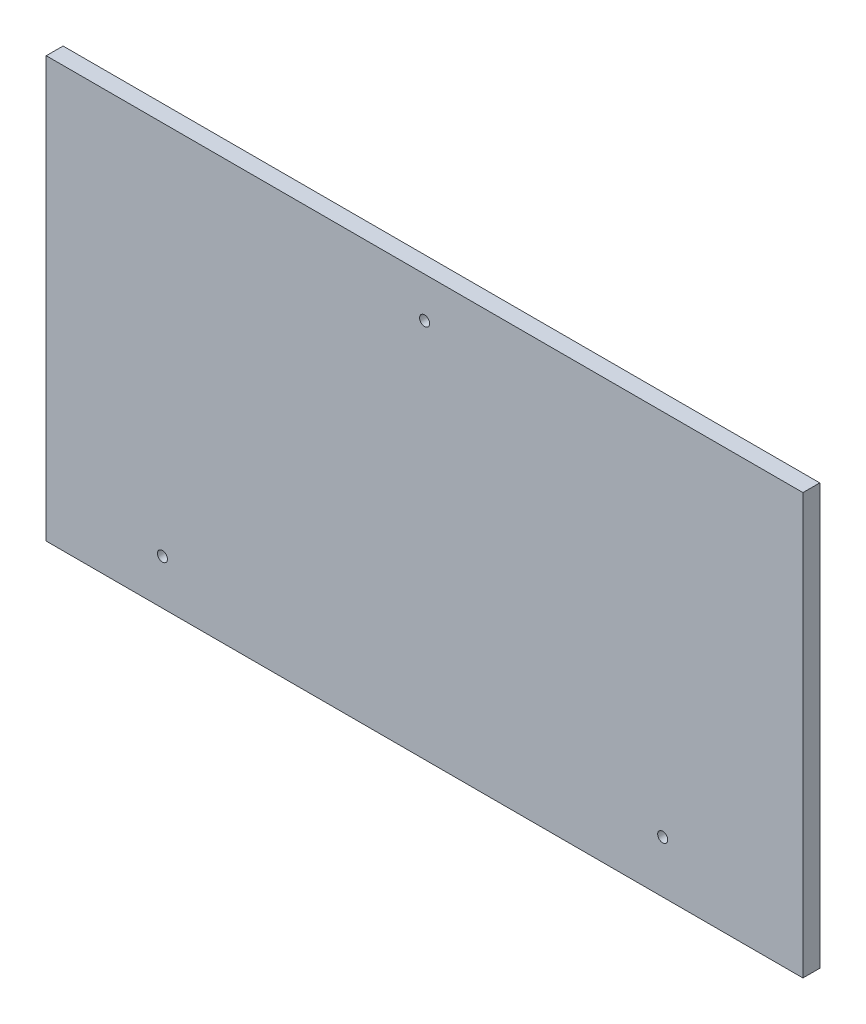
SolidWorks part; units mm, degrees
ref_plane "Ebene vorne" through (0, 0, 0) normal (0, 0, 1) x (1, 0, 0)
ref_plane "Ebene oben" through (0, 0, 0) normal (0, 1, 0) x (1, 0, 0)
ref_plane "Ebene rechts" through (0, 0, 0) normal (1, 0, 0) x (0, 0, -1)
sketch "Skizze1" plane through (0, 0, 0) normal (0, 0, 1) x (1, 0, 0)
  line L2 (225, -125) -> (-225, -125)
  line L3 (225, -125) -> (225, 125)
  line L4 (225, 125) -> (-225, 125)
  line L5 (-225, -125) -> (-225, 125)
  line L6 (225, -125) -> (-225, 125) construction
  line L7 (225, 125) -> (-225, -125) construction
  point P2 (0, 0)
  point P13 (-150.1124, -96.3474)
  point P14 (154.9547, -96.3474)
  point P15 (0, 111.7356)
  point P16 (154.9547, -96.3474)
  dimension "D1" = 450
  dimension "D2" = 250
extrude "Aufsatz-Linear austragen1" add sketch "Skizze1" along normal blind 10 contours L4 L5 L2 L3
sketch "Skizze2" plane through (0, 0, 0) normal (0, 0, -1) x (-1, 0, 0)
  point P0 (-141.608, -94.0978)
  point P1 (155.9071, -98.2492)
  point P2 (0, 101.0168)
hole_wizard "Ø6.0 (6) Durchmesser Bohrung1" positions "3D-Skizze1" profile "Skizze3" hole size "Ø6.0" standard "ISO" end condition through all
sketch3d "3D-Skizze1"
  point P0 (-155.9071, -98.2492, 0)
  point P3 (141.608, -94.0978, 0)
  point P6 (0, 101.0168, 0)
sketch "Skizze3" plane through (-155.9071, -98.2492, 0) normal (1, 0, 0) x (0, 1, 0)
  line L0 (0, 0) -> (0, 10)
  line L1 (0, 10) -> (3, 10)
  line L2 (3, 10) -> (3, 0)
  line L5 (3, 0) -> (0, 0)
  line L11 (0, -6.35) -> (0, 107.95) construction
  dimension "Bohrerdurchmesser" = 6
  dimension "Bohrungstiefe" = 10
